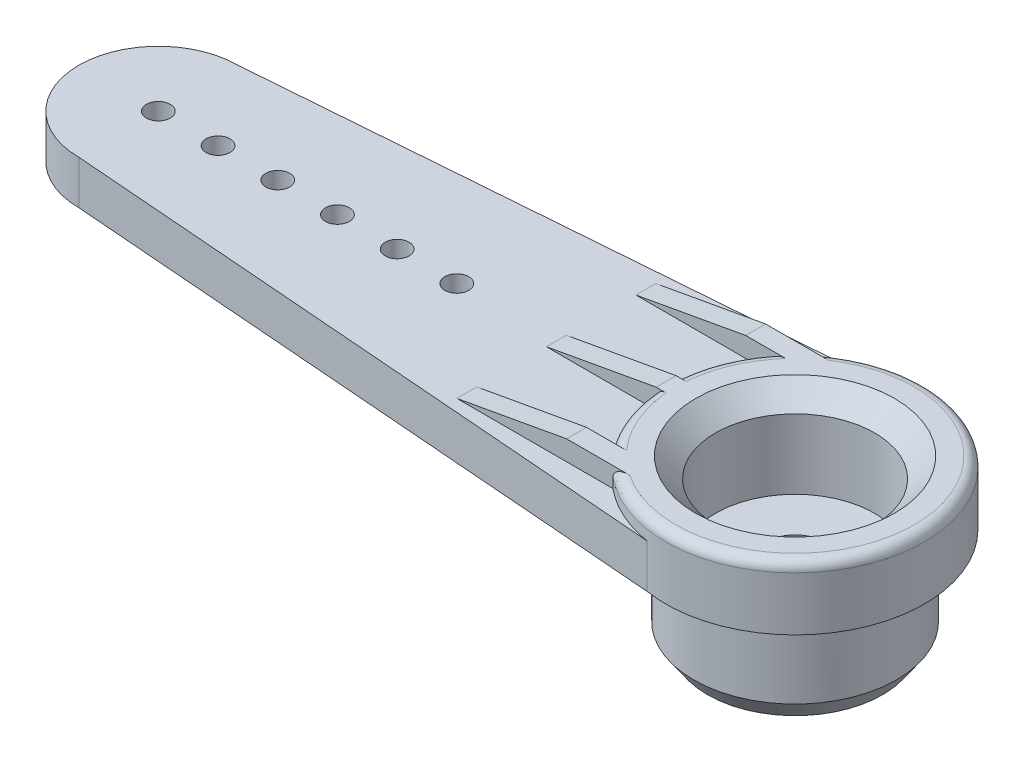
SolidWorks part; units mm, degrees
ref_plane "Спереди" through (0, 0, 0) normal (0, 0, 1) x (1, 0, 0)
ref_plane "Сверху" through (0, 0, 0) normal (0, 1, 0) x (1, 0, 0)
ref_plane "Справа" through (0, 0, 0) normal (1, 0, 0) x (0, 0, -1)
sketch "Эскиз1" plane through (0, 0, 0) normal (0, 1, 0) x (1, 0, 0)
  line L0 (-32, -4) -> (-1.0095, -6.4211)
  line L1 (-32, 4) -> (-1.0095, 6.4211)
  arc A0 (-1.0095, -6.4211) -> (-1.0095, 6.4211) centre (0, 0) ccw
  arc A1 (-32, 4) -> (-32, -4) centre (-32, 0) ccw
  circle A2 centre (-32, 0) radius 0.6
  circle A3 centre (-29, 0) radius 0.6
  circle A4 centre (-26, 0) radius 0.6
  circle A5 centre (-17, 0) radius 0.6
  circle A6 centre (-20, 0) radius 0.6
  circle A7 centre (-23, 0) radius 0.6
  circle A8 centre (0, 0) radius 1.5
extrude "Вытянуть2" add sketch "Эскиз1" along normal blind 8.2
sketch "Эскиз4" plane through (0, 0, 0) normal (0, -1, 0) x (1, 0, 0)
  line L4 (-32, 4.634) -> (0, 7.1582)
  line L5 (-32, -4.634) -> (0, -7.1582)
  circle A0 centre (0, 0) radius 5.1
  arc A1 (0, -7.1582) -> (0, 7.1582) centre (0, 0) ccw
  arc A2 (-32, 4.634) -> (-32, -4.634) centre (-32, 0) ccw
extrude "Вытянуть4" cut sketch "Эскиз4" against normal blind 5
sketch "Эскиз5" plane through (0, 0, 0) normal (0, -1, 0) x (1, 0, 0)
  circle A0 centre (0, 0) radius 3
extrude "Вытянуть5" cut sketch "Эскиз5" against normal blind 3
sketch "Эскиз6" plane through (0, 0, 0) normal (0, -1, 0) x (1, 0, 0)
  circle A0 centre (0, 0) radius 4
  circle A1 centre (0, 0) radius 3
extrude "Вытянуть6" cut sketch "Эскиз6" against normal blind 0.1
chamfer "Фаска1" distance 1 angle 35 1 edges at (0, 0, -5.1) first distance on face at (0, 5, -5.1)
sketch "Эскиз7" plane through (0, 8.2, 0) normal (0, 1, 0) x (1, 0, 0)
  line L1 (-32, 4) -> (-1.0095, 6.4211)
  line L2 (-32, -4) -> (-1.0095, -6.4211)
  arc A0 (-1.0095, 6.4211) -> (-1.0095, -6.4211) centre (0, 0) ccw
  arc A1 (-32, 4) -> (-32, -4) centre (-32, 0) ccw
extrude "Вытянуть7" cut sketch "Эскиз7" against normal blind 1
sketch "Эскиз8" plane through (0, 8.2, 0) normal (0, 1, 0) x (1, 0, 0)
  circle A0 centre (0, 0) radius 4
extrude "Вытянуть8" cut sketch "Эскиз8" against normal blind 4.5
sketch "Эскиз9" plane through (0, 5, 0) normal (0, -1, 0) x (1, 0, 0)
  line L0 (-8, 3.6) -> (-3.6125, 3.6)
  line L1 (-8, -3.6) -> (-3.6125, -3.6)
  line L2 (-8, 3.6) -> (-8, 4.6)
  line L3 (-8, 4.6) -> (-2.2023, 4.6)
  line L4 (-8, -3.6) -> (-8, -4.6)
  line L5 (-8, -4.6) -> (-2.2023, -4.6)
  arc A0 (-2.2023, 4.6) -> (-3.6125, 3.6) centre (0, 0) ccw
  arc A1 (-3.6125, -3.6) -> (-2.2023, -4.6) centre (0, 0) ccw
extrude "Вытянуть9" add sketch "Эскиз9" along normal blind 0.5
sketch "Эскиз10" plane through (0, 0, -4.6) normal (0, 0, -1) x (-1, 0, 0)
  line L0 (8, 4.5) -> (5.1011, 4.5)
  line L1 (8, 4.5) -> (2.2023, 4.5) construction
  line L2 (5.1011, 4.5) -> (8, 5)
  line L4 (8, 5) -> (8, 4.5)
extrude "Вытянуть11" cut sketch "Эскиз10" against normal through all
sketch "Эскиз11" plane through (0, 7.2, 0) normal (0, 1, 0) x (1, 0, 0)
  line L1 (-12, 0) -> (-12, 0.5)
  line L2 (-12, 0.5) -> (-6.4807, 0.5)
  line L3 (-12, 4) -> (-5.1235, 4)
  line L4 (-12, 4) -> (-12, 5)
  line L5 (-12, 5) -> (-4.1533, 5)
  line L6 (-12, -4) -> (-5.1235, -4)
  line L7 (-12, -4) -> (-12, -5)
  line L8 (-12, -5) -> (-4.1533, -5)
  line L9 (-12, 0) -> (-12, -0.5)
  line L10 (-12, -0.5) -> (-6.4807, -0.5)
  arc A0 (-4.1533, 5) -> (-5.1235, 4) centre (0, 0) ccw
  arc A1 (-6.4807, 0.5) -> (-6.4807, -0.5) centre (0, 0) ccw
  arc A2 (-5.1235, -4) -> (-4.1533, -5) centre (0, 0) ccw
extrude "Вытянуть12" add sketch "Эскиз11" along normal blind 1
sketch "Эскиз12" plane through (0, 0, 5) normal (0, 0, 1) x (1, 0, 0)
  line L0 (-6.4807, 8.2) -> (-12, 7.2)
  line L1 (-12, 8.2) -> (-12, 7.2) construction
  line L2 (-32, 7.2) -> (-1.0095, 7.2) construction
  line L3 (-12, 7.2) -> (-12, 8.2)
  line L4 (-12, 8.2) -> (-6.4807, 8.2)
extrude "Вытянуть13" cut sketch "Эскиз12" against normal through all
chamfer "Фаска2" distance 1 angle 45 1 edges at (0, 8.2, 4)
fillet "Скругление1" radius 0.5 3 edges at (-6.0603, 8.2, 2.3501) (-6.0603, 8.2, -2.3501) (6.5, 8.2, 0)
